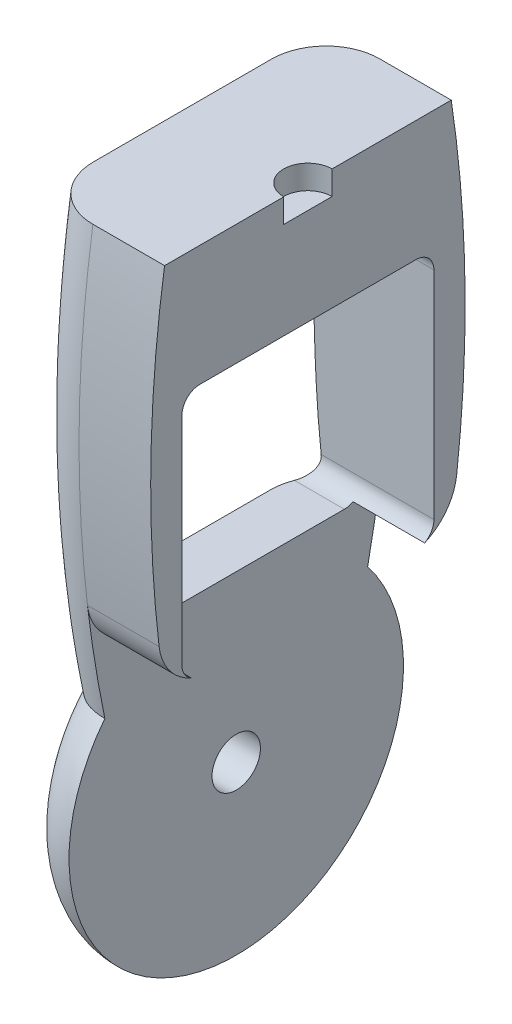
SolidWorks part; units mm, degrees
ref_plane "Front Plane" through (0, 0, 0) normal (0, 0, 1) x (1, 0, 0)
ref_plane "Top Plane" through (0, 0, 0) normal (0, 1, 0) x (1, 0, 0)
ref_plane "Right Plane" through (0, 0, 0) normal (1, 0, 0) x (0, 0, -1)
sketch "Sketch1" plane through (0, 0, 0) normal (1, 0, 0) x (0, 0, -1)
  line L0 (0, 0) -> (0, 86.1529) construction
  line L1 (-24, 90) -> (24, 90)
  circle A0 centre (0, 0) radius 28
  arc A1 (24, 90) -> (22, 17.3205) centre (-178.6745, 59.21) cw
  arc A2 (-24, 90) -> (-22, 17.3205) centre (178.6745, 59.21) ccw
  dimension "D1" = 56
  dimension "D3" = 205
  dimension "D2" = 24
  dimension "D4" = 90
  dimension "D5" = 22
extrude "Boss-Extrude1" add sketch "Sketch1" along normal blind 21 contours A0 L0 L1 | L0 A0 L1 | A0 region at (0, 57.3311, 0) region at (0, 0, 0)
sketch "Sketch2" plane through (0, 0, 0) normal (1, 0, 0) x (0, 0, -1)
  circle A0 centre (0, 0) radius 4.05
  circle A1 centre (0, 0) radius 11
  dimension "D1" = 8.1
  dimension "D2" = 22
extrude "Cut-Extrude1" cut sketch "Sketch2" along normal up to next contours A0
sketch "Sketch3" plane through (0, 0, 0) normal (1, 0, 0) x (0, 0, -1)
  line L0 (-24, 90) -> (24, 90) construction
  line L1 (21.1, 35.5) -> (-21.1, 35.5)
  line L2 (21.1, 35.5) -> (21.1, 74.5)
  line L3 (21.1, 74.5) -> (-21.1, 74.5)
  line L4 (-21.1, 35.5) -> (-21.1, 74.5)
  line L5 (21.1, 35.5) -> (-21.1, 74.5) construction
  line L6 (21.1, 74.5) -> (-21.1, 35.5) construction
  line L7 (11.5, 76.5) -> (-11.5, 76.5)
  line L8 (11.5, 76.5) -> (11.5, 72.5)
  line L9 (11.5, 72.5) -> (-11.5, 72.5)
  line L10 (-11.5, 76.5) -> (-11.5, 72.5)
  line L11 (11.5, 76.5) -> (-11.5, 72.5) construction
  line L12 (11.5, 72.5) -> (-11.5, 76.5) construction
  line L17 (2.65, 63) -> (-2.65, 63)
  line L18 (2.65, 63) -> (2.65, 90)
  line L19 (2.65, 90) -> (-2.65, 90)
  line L20 (-2.65, 63) -> (-2.65, 90)
  line L21 (2.65, 63) -> (-2.65, 90) construction
  line L22 (2.65, 90) -> (-2.65, 63) construction
  point P0 (0, 55)
  point P5 (0, 74.5)
  point P11 (0, 76.5)
  dimension "D1" = 39
  dimension "D2" = 42.2
  dimension "D3" = 2
  dimension "D4" = 23
  dimension "D5" = 5.3
  dimension "D6" = 55
sketch "Sketch4" plane through (0, 0, 0) normal (0, 0, 1) x (1, 0, 0)
  line L1 (32.9092, -28) -> (9, -28)
  line L2 (32.9092, -28) -> (32.9092, 28)
  line L3 (32.9092, 28) -> (9, 28)
  line L4 (9, -28) -> (9, 28)
  line L5 (32.9092, -28) -> (9, 28) construction
  line L6 (32.9092, 28) -> (9, -28) construction
  point P0 (20.9546, 0)
  dimension "D1" = 56
  dimension "D2" = 9
extrude "Cut-Extrude2" cut sketch "Sketch4" against normal through all both and the other way through all
sketch "Sketch5" plane through (0, 0, 0) normal (1, 0, 0) x (0, 0, -1)
  line L1 (-15.5, 33.225) -> (15.5, 33.225) construction
  line L2 (-15.5, 33.225) -> (-15.5, 64.225) construction
  line L3 (-15.5, 64.225) -> (15.5, 64.225) construction
  line L4 (15.5, 33.225) -> (15.5, 64.225) construction
  line L5 (-15.5, 33.225) -> (15.5, 64.225) construction
  line L6 (-15.5, 64.225) -> (15.5, 33.225) construction
  line L7 (-18.1, 27.625) -> (18.1, 27.625)
  line L8 (-21.1, 30.625) -> (-21.1, 66.825)
  line L9 (-18.1, 69.825) -> (18.1, 69.825)
  line L10 (21.1, 30.625) -> (21.1, 66.825)
  line L11 (-21.1, 27.625) -> (21.1, 69.825) construction
  line L12 (-21.1, 69.825) -> (21.1, 27.625) construction
  circle A0 centre (-15.5, 33.225) radius 1.55
  circle A1 centre (15.5, 33.225) radius 1.55
  circle A2 centre (15.5, 64.225) radius 1.55
  circle A3 centre (-15.5, 64.225) radius 1.55
  arc A4 (-21.1, 66.825) -> (-18.1, 69.825) centre (-18.1, 66.825) cw
  arc A5 (18.1, 69.825) -> (21.1, 66.825) centre (18.1, 66.825) cw
  arc A6 (18.1, 27.625) -> (21.1, 30.625) centre (18.1, 30.625) ccw
  arc A7 (-18.1, 27.625) -> (-21.1, 30.625) centre (-18.1, 30.625) cw
  point P0 (0, 48.725)
  point P11 (0, 48.725)
  dimension "D1" = 3.1
  dimension "D7" = 3
  dimension "D2" = 31
  dimension "D3" = 31
  dimension "D4" = 48.725
  dimension "D5" = 42.2
  dimension "D6" = 42.2
extrude "Cut-Extrude3" cut sketch "Sketch5" along normal through all contours L8 A4 L9 A5 L10 A6 L7 A7
fillet "Fillet1" radius 9 3 edges at (0, 53.5709, -26.2479) (0, 53.5709, 26.2479) (0, -28, 0)
fillet "Fillet2" radius 9 2 edges at (15, 28, -23.9358) (15, 28, 23.9358)
sketch "Sketch6" plane through (0, 0, 0) normal (0, 1, 0) x (1, 0, 0)
  circle A0 centre (21, 0) radius 4.05
  point P2 (0, 0)
  dimension "D1" = 8.1
  dimension "D2" = 21
extrude "Cut-Extrude4" cut sketch "Sketch6" against normal blind 4 from surface starting at face at (9.4067, 90, -0.2348)
equation "\"gear dist\"= 48.725"
equation "\"arm dia\"= 56"
equation "\"arm top width\"= 24"
equation "\"arm length\"=90"
equation "\"D4@Sketch1\"=\"arm length\""
equation "\"arm bottom width\"=22"
equation "\"D5@Sketch1\"=\"arm bottom width\""
equation "\"arm radius\"=205"
equation "\"D3@Sketch1\"=\"arm radius\""
equation "\"D2@Sketch1\"= \"arm top width\""
equation "\"D1@Sketch1\"= \"arm dia\""
equation "\"bearing bore\"= 8.1'bear"
equation "\"bearing OD\"= 22"
equation "\"bearing depth\"= 7.1"
equation "\"stepper motor hole dist\"= 31"
equation "\"M3 hole\"= 3.1"
equation "\"M3 head\"= 6.2"
equation "\"arm width\"= 42"
equation "\"D1@Boss-Extrude1\"=\"arm width\"/2"
equation "\"D1@Sketch2\"=\"bearing bore\""
equation "\"D2@Sketch2\"=\"bearing OD\""
equation "\"stepper motor height\"=39"
equation "\"D1@Sketch3\"=\"stepper motor height\""
equation "\"dist to stepper motor\"=55"
equation "\"D6@Sketch3\"=\"dist to stepper motor\""
equation "\"stepper motor width\"=42.2"
equation "\"D2@Sketch3\"=\"stepper motor width\""
equation "\"D1@Sketch4\"=\"arm dia\""
equation "\"D2@Sketch5\"=\"stepper motor hole dist\""
equation "\"D4@Sketch5\"=\"gear dist\""
equation "\"D3@Sketch5\"=\"stepper motor hole dist\""
equation "\"D5@Sketch5\"=\"stepper motor width\""
equation "\"D6@Sketch5\"=\"stepper motor width\""
equation "\"D1@Sketch5\"=\"M3 hole\""
equation "\"D2@Sketch6\"=\"arm width\"/2"
